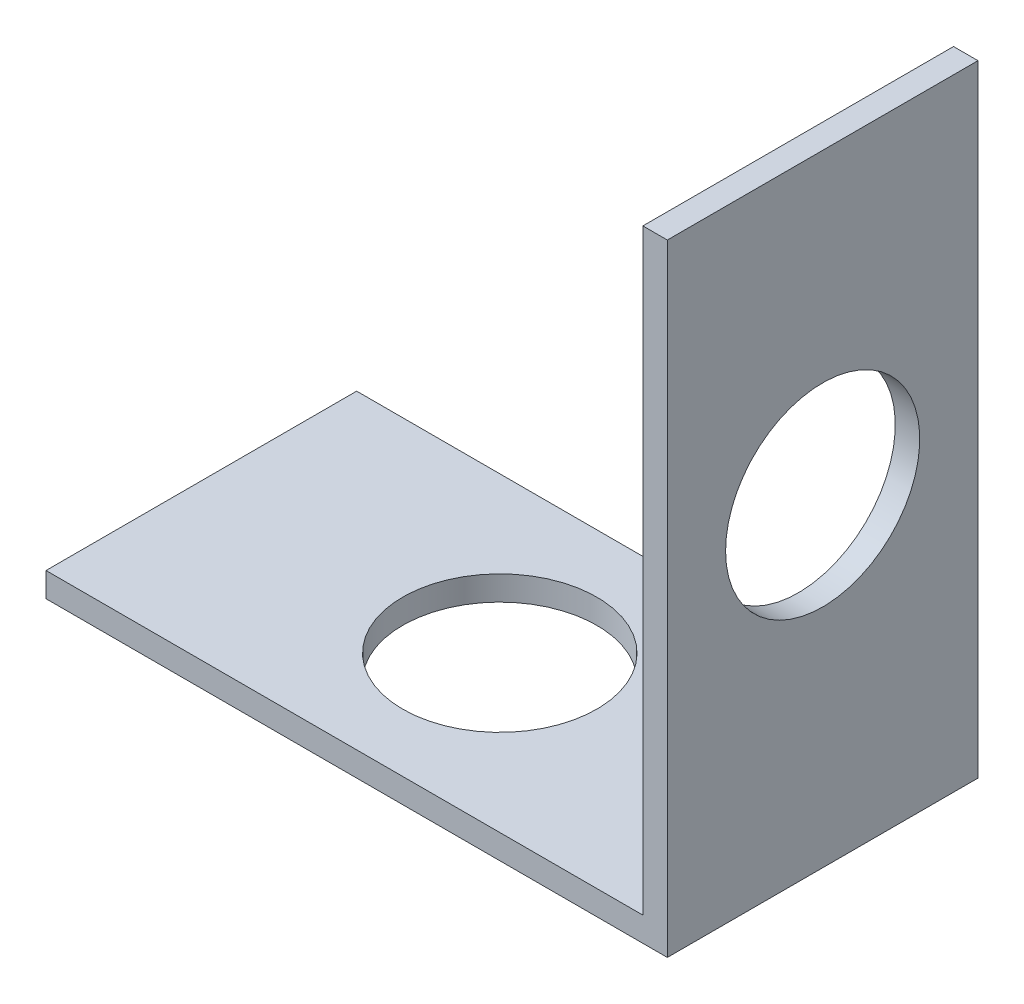
SolidWorks part; units mm, degrees
material "6061 Alloy"
ref_plane "Front Plane" through (0, 0, 0) normal (0, 0, 1) x (1, 0, 0)
ref_plane "Top Plane" through (0, 0, 0) normal (0, 1, 0) x (1, 0, 0)
ref_plane "Right Plane" through (0, 0, 0) normal (1, 0, 0) x (0, 0, -1)
sketch "Sketch1" plane through (0, 0, 0) normal (0, 0, 1) x (1, 0, 0)
  line L0 (0, 0) -> (0, 25.4)
  line L1 (0, 0) -> (-25.4, 0)
  line L2 (-1, 1) -> (-25.4, 1)
  line L3 (-1, 1) -> (-1, 25.4)
  line L4 (-25.4, 1) -> (-25.4, 0)
  line L5 (-1, 25.4) -> (0, 25.4)
  dimension "D1" = 1
  dimension "D2" = 25.4
  dimension "D3" = 25.4
extrude "Boss-Extrude1" add sketch "Sketch1" along normal mid plane 12.7
sketch "Sketch2" plane through (-1, 0, 0) normal (-1, 0, 0) x (0, 0, 1)
  line L0 (0, 25.4) -> (0, 1) construction
  line L1 (6.35, 25.4) -> (-6.35, 25.4) construction
  line L2 (6.35, 1) -> (-6.35, 1) construction
  line L3 (-6.35, 13.2) -> (6.35, 13.2) construction
  line L4 (-6.35, 25.4) -> (-6.35, 1) construction
  line L5 (6.35, 25.4) -> (6.35, 1) construction
  point P0 (0, 13.2)
hole_wizard "5/16 (0.3125) Diameter Hole1" positions "Sketch3" profile "Sketch4" hole size "5/16" standard "ANSI Inch" end condition through all
sketch "Sketch3" plane through (-1, 0, 0) normal (-1, 0, 0) x (0, 0, 1)
  point P0 (0, 13.2)
sketch "Sketch4" plane through (-1, 13.2, 0) normal (0, 1, 0) x (0, 0, 1)
  line L0 (0, 0) -> (0, 1)
  line L1 (0, 1) -> (3.9688, 1)
  line L2 (3.9688, 1) -> (3.9688, 0)
  line L5 (3.9688, 0) -> (0, 0)
  line L11 (0, -6.35) -> (0, 107.95) construction
  dimension "Thru Hole Dia." = 7.9375
  dimension "Thru Hole Depth" = 1
sketch "Sketch5" plane through (0, 1, 0) normal (0, 1, 0) x (1, 0, 0)
  line L0 (-13.2, 6.35) -> (-13.2, -6.35) construction
  line L1 (-1, 6.35) -> (-25.4, 6.35) construction
  line L2 (-1, -6.35) -> (-25.4, -6.35) construction
  line L3 (-25.4, 0) -> (-1, 0) construction
  line L4 (-25.4, -6.35) -> (-25.4, 6.35) construction
  point P11 (-13.2, 0)
hole_wizard "5/16 (0.3125) Diameter Hole2" positions "3DSketch1" profile "Sketch6" hole size "5/16" standard "ANSI Inch" end condition through all
sketch3d "3DSketch1"
  point P0 (-13.2, 1, 0)
sketch "Sketch6" plane through (-13.2, 1, 0) normal (1, 0, 0) x (0, 0, 1)
  line L0 (0, 0) -> (0, 1)
  line L1 (0, 1) -> (3.9688, 1)
  line L2 (3.9688, 1) -> (3.9687, 0)
  line L5 (3.9687, 0) -> (0, 0)
  line L11 (0, -6.35) -> (0, 107.95) construction
  dimension "Thru Hole Dia." = 7.9375
  dimension "Thru Hole Depth" = 1
